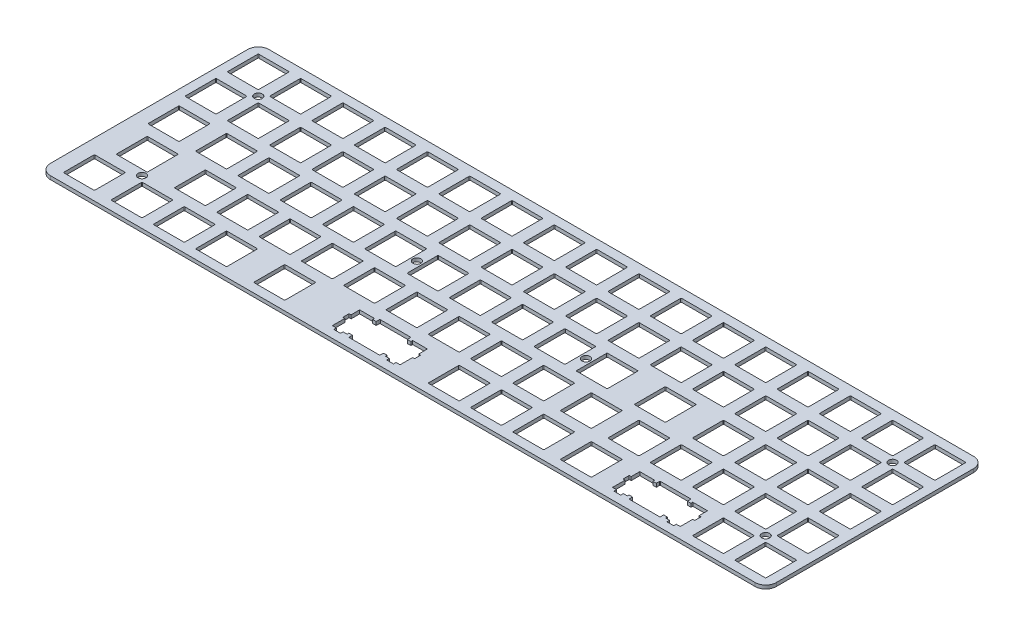
SolidWorks part; units mm, degrees
ref_plane "Front" through (0, 0, 0) normal (0, 0, 1) x (1, 0, 0)
ref_plane "Top" through (0, 0, 0) normal (0, 1, 0) x (1, 0, 0)
ref_plane "Right" through (0, 0, 0) normal (1, 0, 0) x (0, 0, -1)
sketch "Sketch1" plane through (0, 0, 0) normal (0, 1, 0) x (1, 0, 0)
  line L0 (-161.925, 28.575) -> (161.925, 28.575)
  line L1 (161.925, -47.625) -> (-161.925, -47.625)
  line L2 (161.925, -47.625) -> (161.925, 47.625)
  line L3 (161.925, 47.625) -> (-161.925, 47.625)
  line L4 (-161.925, -47.625) -> (-161.925, 47.625)
  line L5 (-123.825, 47.625) -> (-123.825, 28.575)
  line L6 (-104.775, 47.625) -> (-104.775, 28.575)
  line L7 (-142.875, 47.625) -> (-142.875, 28.575)
  line L8 (-85.725, 47.625) -> (-85.725, 28.575)
  line L9 (-66.675, 47.625) -> (-66.675, 28.575)
  line L10 (-47.625, 47.625) -> (-47.625, 28.575)
  line L11 (-28.575, 47.625) -> (-28.575, 28.575)
  line L12 (-9.525, 47.625) -> (-9.525, 28.575)
  line L13 (9.525, 47.625) -> (9.525, 28.575)
  line L14 (28.575, 47.625) -> (28.575, 28.575)
  line L15 (47.625, 47.625) -> (47.625, 28.575)
  line L16 (66.675, 47.625) -> (66.675, 28.575)
  line L17 (85.725, 47.625) -> (85.725, 28.575)
  line L18 (104.775, 47.625) -> (104.775, 28.575)
  line L19 (123.825, 47.625) -> (123.825, 28.575)
  line L20 (142.875, 47.625) -> (142.875, 28.575)
  line L21 (-142.875, 47.625) -> (-123.825, 47.625) construction
  line L22 (-161.925, 9.525) -> (161.925, 9.525)
  line L23 (-142.875, 28.575) -> (-142.875, 9.525)
  line L24 (-123.825, 28.575) -> (-123.825, 9.525)
  line L25 (-104.775, 28.575) -> (-104.775, 9.525)
  line L26 (-85.725, 28.575) -> (-85.725, 9.525)
  line L27 (-66.675, 28.575) -> (-66.675, 9.525)
  line L28 (-47.625, 28.575) -> (-47.625, 9.525)
  line L29 (-28.575, 28.575) -> (-28.575, 9.525)
  line L30 (-9.525, 28.575) -> (-9.525, 9.525)
  line L31 (9.525, 28.575) -> (9.525, 9.525)
  line L32 (28.575, 28.575) -> (28.575, 9.525)
  line L33 (47.625, 28.575) -> (47.625, 9.525)
  line L34 (66.675, 28.575) -> (66.675, 9.525)
  line L35 (85.725, 28.575) -> (85.725, 9.525)
  line L36 (104.775, 28.575) -> (104.775, 9.525)
  line L37 (123.825, 28.575) -> (123.825, 9.525)
  line L38 (142.875, 28.575) -> (142.875, 9.525)
  line L39 (-142.875, 28.575) -> (-123.825, 28.575) construction
  line L40 (-161.925, -9.525) -> (161.925, -9.525)
  line L41 (-161.925, -28.575) -> (161.925, -28.575)
  line L42 (-138.1125, 9.525) -> (-138.1125, -9.525)
  line L43 (-128.5875, -9.525) -> (-128.5875, -28.575)
  line L44 (-138.1125, -28.575) -> (-138.1125, -47.625)
  line L45 (-119.0625, 9.525) -> (-119.0625, -9.525)
  line L46 (-100.0125, 9.525) -> (-100.0125, -9.525)
  line L47 (-80.9625, 9.525) -> (-80.9625, -9.525)
  line L48 (-61.9125, 9.525) -> (-61.9125, -9.525)
  line L49 (-42.8625, 9.525) -> (-42.8625, -9.525)
  line L50 (-23.8125, 9.525) -> (-23.8125, -9.525)
  line L51 (-4.7625, 9.525) -> (-4.7625, -9.525)
  line L52 (14.2875, 9.525) -> (14.2875, -9.525)
  line L53 (33.3375, 9.525) -> (33.3375, -9.525)
  line L54 (-138.1125, 9.525) -> (-119.0625, 9.525) construction
  line L55 (52.3875, 9.525) -> (52.3875, -9.525)
  line L56 (85.725, 9.525) -> (85.725, -9.525)
  line L57 (-109.5375, -9.525) -> (-109.5375, -28.575)
  line L58 (-90.4875, -9.525) -> (-90.4875, -28.575)
  line L59 (-71.4375, -9.525) -> (-71.4375, -28.575)
  line L60 (-52.3875, -9.525) -> (-52.3875, -28.575)
  line L61 (-33.3375, -9.525) -> (-33.3375, -28.575)
  line L62 (-14.2875, -9.525) -> (-14.2875, -28.575)
  line L63 (4.7625, -9.525) -> (4.7625, -28.575)
  line L64 (23.8125, -9.525) -> (23.8125, -28.575)
  line L65 (42.8625, -9.525) -> (42.8625, -28.575)
  line L66 (-128.5875, -9.525) -> (-109.5375, -9.525) construction
  line L67 (66.675, -9.525) -> (66.675, -28.575)
  line L68 (85.725, -9.525) -> (85.725, -28.575)
  line L69 (-119.0625, -28.575) -> (-119.0625, -47.625)
  line L70 (-100.0125, -28.575) -> (-100.0125, -47.625)
  line L71 (-80.9625, -28.575) -> (-80.9625, -47.625)
  line L72 (-138.1125, -28.575) -> (-119.0625, -28.575) construction
  line L73 (-47.625, -28.575) -> (-47.625, -47.625)
  line L74 (4.7625, -28.575) -> (4.7625, -47.625)
  line L75 (23.8125, -28.575) -> (23.8125, -47.625)
  line L76 (42.8625, -28.575) -> (42.8625, -47.625)
  line L77 (61.9125, -28.575) -> (61.9125, -47.625)
  line L78 (85.725, -28.575) -> (85.725, -47.625)
  line L79 (104.775, 9.525) -> (104.775, -9.525)
  line L80 (104.775, -9.525) -> (104.775, -28.575)
  line L81 (123.825, 9.525) -> (123.825, -9.525)
  line L82 (123.825, -9.525) -> (123.825, -28.575)
  line L83 (123.825, -28.575) -> (123.825, -47.625)
  line L84 (142.875, 9.525) -> (142.875, -9.525)
  line L85 (142.875, -9.525) -> (142.875, -28.575)
  line L86 (142.875, -28.575) -> (142.875, -47.625)
  line L87 (-161.925, 47.625) -> (-142.875, 28.575) construction
  line L88 (-142.875, 28.575) -> (-161.925, 9.525) construction
  line L89 (-161.925, 9.525) -> (-138.1125, -9.525) construction
  line L90 (-138.1125, -9.525) -> (-119.0625, 9.525) construction
  line L91 (-119.0625, 9.525) -> (-100.0125, -9.525) construction
  line L92 (-100.0125, -9.525) -> (-80.9625, 9.525) construction
  line L93 (-80.9625, 9.525) -> (-61.9125, -9.525) construction
  line L94 (-61.9125, -9.525) -> (-42.8625, 9.525) construction
  line L95 (-42.8625, 9.525) -> (-23.8125, -9.525) construction
  line L96 (-23.8125, -9.525) -> (-4.7625, 9.525) construction
  line L97 (-4.7625, 9.525) -> (14.2875, -9.525) construction
  line L98 (14.2875, -9.525) -> (33.3375, 9.525) construction
  line L99 (33.3375, 9.525) -> (52.3875, -9.525) construction
  line L100 (52.3875, -9.525) -> (85.725, 9.525) construction
  line L101 (85.725, 9.525) -> (104.775, -9.525) construction
  line L102 (104.775, -9.525) -> (85.725, -28.575) construction
  line L103 (85.725, -47.625) -> (123.825, -28.575) construction
  line L104 (85.725, -28.575) -> (123.825, -47.625) construction
  line L105 (123.825, -28.575) -> (104.775, -9.525) construction
  line L106 (104.775, -9.525) -> (123.825, 9.525) construction
  line L107 (123.825, 9.525) -> (104.775, 28.575) construction
  line L108 (104.775, 28.575) -> (123.825, 47.625) construction
  line L109 (123.825, 47.625) -> (142.875, 28.575) construction
  line L110 (142.875, 28.575) -> (123.825, 9.525) construction
  line L111 (123.825, 9.525) -> (142.875, -9.525) construction
  line L112 (142.875, -9.525) -> (123.825, -28.575) construction
  line L113 (123.825, -28.575) -> (142.875, -47.625) construction
  line L114 (142.875, -47.625) -> (161.925, -28.575) construction
  line L115 (161.925, -28.575) -> (142.875, -9.525) construction
  line L116 (142.875, -9.525) -> (161.925, 9.525) construction
  line L117 (161.925, 9.525) -> (142.875, 28.575) construction
  line L118 (142.875, 28.575) -> (161.925, 47.625) construction
  line L119 (161.925, -47.625) -> (142.875, -28.575) construction
  line L120 (142.875, -28.575) -> (123.825, -47.625) construction
  line L121 (85.725, -47.625) -> (61.9125, -28.575) construction
  line L122 (61.9125, -28.575) -> (42.8625, -47.625) construction
  line L123 (42.8625, -47.625) -> (23.8125, -28.575) construction
  line L124 (23.8125, -28.575) -> (42.8625, -9.525) construction
  line L125 (42.8625, -9.525) -> (66.675, -28.575) construction
  line L126 (66.675, -28.575) -> (85.725, -9.525) construction
  line L127 (85.725, -9.525) -> (104.775, -28.575) construction
  line L128 (104.775, -28.575) -> (123.825, -9.525) construction
  line L129 (123.825, -9.525) -> (142.875, -28.575) construction
  line L130 (142.875, -28.575) -> (161.925, -9.525) construction
  line L131 (161.925, -9.525) -> (142.875, 9.525) construction
  line L132 (142.875, 9.525) -> (123.825, -9.525) construction
  line L133 (123.825, -9.525) -> (104.775, 9.525) construction
  line L134 (104.775, 9.525) -> (85.725, -9.525) construction
  line L135 (85.725, -9.525) -> (52.3875, 9.525) construction
  line L136 (52.3875, 9.525) -> (33.3375, -9.525) construction
  line L137 (33.3375, -9.525) -> (14.2875, 9.525) construction
  line L138 (14.2875, 9.525) -> (-4.7625, -9.525) construction
  line L139 (-4.7625, -9.525) -> (-23.8125, 9.525) construction
  line L140 (-23.8125, 9.525) -> (-42.8625, -9.525) construction
  line L141 (-42.8625, -9.525) -> (-61.9125, 9.525) construction
  line L142 (-61.9125, 9.525) -> (-80.9625, -9.525) construction
  line L143 (-80.9625, -9.525) -> (-100.0125, 9.525) construction
  line L144 (-100.0125, 9.525) -> (-119.0625, -9.525) construction
  line L145 (-119.0625, -9.525) -> (-138.1125, 9.525) construction
  line L146 (-138.1125, 9.525) -> (-161.925, -9.525) construction
  line L147 (-161.925, -9.525) -> (-128.5875, -28.575) construction
  line L148 (-128.5875, -28.575) -> (-109.5375, -9.525) construction
  line L149 (-109.5375, -9.525) -> (-90.4875, -28.575) construction
  line L150 (-90.4875, -28.575) -> (-71.4375, -9.525) construction
  line L151 (-71.4375, -9.525) -> (-52.3875, -28.575) construction
  line L152 (-52.3875, -28.575) -> (-33.3375, -9.525) construction
  line L153 (-33.3375, -9.525) -> (-14.2875, -28.575) construction
  line L154 (-14.2875, -28.575) -> (4.7625, -9.525) construction
  line L155 (4.7625, -9.525) -> (23.8125, -28.575) construction
  line L156 (23.8125, -28.575) -> (4.7625, -47.625) construction
  line L157 (4.7625, -47.625) -> (-47.625, -28.575) construction
  line L158 (-47.625, -28.575) -> (-80.9625, -47.625) construction
  line L159 (-80.9625, -47.625) -> (-100.0125, -28.575) construction
  line L160 (-100.0125, -28.575) -> (-119.0625, -47.625) construction
  line L161 (-119.0625, -47.625) -> (-138.1125, -28.575) construction
  line L162 (-138.1125, -28.575) -> (-161.925, -47.625) construction
  line L163 (-161.925, -28.575) -> (-138.1125, -47.625) construction
  line L164 (-138.1125, -47.625) -> (-119.0625, -28.575) construction
  line L165 (-119.0625, -28.575) -> (-100.0125, -47.625) construction
  line L166 (-100.0125, -47.625) -> (-80.9625, -28.575) construction
  line L167 (-80.9625, -28.575) -> (-47.625, -47.625) construction
  line L168 (-47.625, -47.625) -> (4.7625, -28.575) construction
  line L169 (4.7625, -28.575) -> (23.8125, -47.625) construction
  line L170 (23.8125, -47.625) -> (42.8625, -28.575) construction
  line L171 (42.8625, -28.575) -> (61.9125, -47.625) construction
  line L172 (61.9125, -47.625) -> (85.725, -28.575) construction
  line L173 (85.725, -28.575) -> (66.675, -9.525) construction
  line L174 (66.675, -9.525) -> (42.8625, -28.575) construction
  line L175 (42.8625, -28.575) -> (23.8125, -9.525) construction
  line L176 (23.8125, -9.525) -> (4.7625, -28.575) construction
  line L177 (4.7625, -28.575) -> (-14.2875, -9.525) construction
  line L178 (-14.2875, -9.525) -> (-33.3375, -28.575) construction
  line L179 (-33.3375, -28.575) -> (-52.3875, -9.525) construction
  line L180 (-52.3875, -9.525) -> (-71.4375, -28.575) construction
  line L181 (-71.4375, -28.575) -> (-90.4875, -9.525) construction
  line L182 (-90.4875, -9.525) -> (-109.5375, -28.575) construction
  line L183 (-109.5375, -28.575) -> (-128.5875, -9.525) construction
  line L184 (-128.5875, -9.525) -> (-161.925, -28.575) construction
  line L185 (161.925, 28.575) -> (142.875, 9.525) construction
  line L186 (142.875, 9.525) -> (123.825, 28.575) construction
  line L187 (123.825, 28.575) -> (104.775, 9.525) construction
  line L188 (104.775, 9.525) -> (85.725, 28.575) construction
  line L189 (85.725, 28.575) -> (66.675, 9.525) construction
  line L190 (66.675, 9.525) -> (47.625, 28.575) construction
  line L191 (47.625, 28.575) -> (28.575, 9.525) construction
  line L192 (28.575, 9.525) -> (9.525, 28.575) construction
  line L193 (9.525, 28.575) -> (-9.525, 9.525) construction
  line L194 (-9.525, 9.525) -> (-28.575, 28.575) construction
  line L195 (-28.575, 28.575) -> (-47.625, 9.525) construction
  line L196 (-47.625, 9.525) -> (-66.675, 28.575) construction
  line L197 (-66.675, 28.575) -> (-85.725, 9.525) construction
  line L198 (-85.725, 9.525) -> (-104.775, 28.575) construction
  line L199 (-104.775, 28.575) -> (-123.825, 9.525) construction
  line L200 (-123.825, 9.525) -> (-142.875, 28.575) construction
  line L201 (-161.925, 28.575) -> (-142.875, 9.525) construction
  line L202 (-142.875, 9.525) -> (-123.825, 28.575) construction
  line L203 (-123.825, 28.575) -> (-104.775, 9.525) construction
  line L204 (-104.775, 9.525) -> (-85.725, 28.575) construction
  line L205 (-85.725, 28.575) -> (-66.675, 9.525) construction
  line L206 (-66.675, 9.525) -> (-47.625, 28.575) construction
  line L207 (-47.625, 28.575) -> (-28.575, 9.525) construction
  line L208 (-28.575, 9.525) -> (-9.525, 28.575) construction
  line L209 (-9.525, 28.575) -> (9.525, 9.525) construction
  line L210 (9.525, 9.525) -> (28.575, 28.575) construction
  line L211 (28.575, 28.575) -> (47.625, 9.525) construction
  line L212 (47.625, 9.525) -> (66.675, 28.575) construction
  line L213 (66.675, 28.575) -> (85.725, 9.525) construction
  line L214 (85.725, 9.525) -> (104.775, 28.575) construction
  line L215 (161.925, 28.575) -> (142.875, 47.625) construction
  line L216 (142.875, 47.625) -> (123.825, 28.575) construction
  line L217 (123.825, 28.575) -> (104.775, 47.625) construction
  line L218 (104.775, 47.625) -> (85.725, 28.575) construction
  line L219 (85.725, 28.575) -> (66.675, 47.625) construction
  line L220 (66.675, 47.625) -> (47.625, 28.575) construction
  line L221 (47.625, 28.575) -> (28.575, 47.625) construction
  line L222 (28.575, 47.625) -> (9.525, 28.575) construction
  line L223 (9.525, 28.575) -> (-9.525, 47.625) construction
  line L224 (-9.525, 47.625) -> (-28.575, 28.575) construction
  line L225 (-28.575, 28.575) -> (-47.625, 47.625) construction
  line L226 (-47.625, 47.625) -> (-66.675, 28.575) construction
  line L227 (-66.675, 28.575) -> (-85.725, 47.625) construction
  line L228 (-85.725, 47.625) -> (-104.775, 28.575) construction
  line L229 (-104.775, 28.575) -> (-123.825, 47.625) construction
  line L230 (-123.825, 47.625) -> (-142.875, 28.575) construction
  line L231 (-161.925, 28.575) -> (-142.875, 47.625) construction
  line L232 (-142.875, 47.625) -> (-123.825, 28.575) construction
  line L233 (-123.825, 28.575) -> (-104.775, 47.625) construction
  line L234 (-104.775, 47.625) -> (-85.725, 28.575) construction
  line L235 (-85.725, 28.575) -> (-66.675, 47.625) construction
  line L236 (-66.675, 47.625) -> (-47.625, 28.575) construction
  line L237 (-47.625, 28.575) -> (-28.575, 47.625) construction
  line L238 (-28.575, 47.625) -> (-9.525, 28.575) construction
  line L239 (-9.525, 28.575) -> (9.525, 47.625) construction
  line L240 (9.525, 47.625) -> (28.575, 28.575) construction
  line L241 (28.575, 28.575) -> (47.625, 47.625) construction
  line L242 (47.625, 47.625) -> (66.675, 28.575) construction
  line L243 (66.675, 28.575) -> (85.725, 47.625) construction
  line L244 (85.725, 47.625) -> (104.775, 28.575) construction
  line L245 (160.147, 50.6095) -> (-160.147, 50.6095)
  line L246 (164.9095, 45.847) -> (164.9095, -45.847)
  line L247 (160.147, -50.6095) -> (-160.147, -50.6095)
  line L248 (-164.9095, 45.847) -> (-164.9095, -45.847)
  arc A0 (164.9095, 45.847) -> (160.147, 50.6095) centre (160.147, 45.847) ccw
  arc A1 (160.147, -50.6095) -> (164.9095, -45.847) centre (160.147, -45.847) ccw
  arc A2 (-164.9095, -45.847) -> (-160.147, -50.6095) centre (-160.147, -45.847) ccw
  arc A3 (-160.147, 50.6095) -> (-164.9095, 45.847) centre (-160.147, 45.847) ccw
  point P145 (0, 0)
  point P146 (104.775, -38.1)
  point P147 (-152.4, 38.1)
  point P148 (-152.4, 19.05)
  point P149 (-150.0188, 0)
  point P150 (-145.2562, -19.05)
  point P151 (-150.0188, -38.1)
  point P152 (-128.5875, -38.1)
  point P153 (-119.0625, -19.05)
  point P154 (-128.5875, 0)
  point P155 (-133.35, 19.05)
  point P156 (-133.35, 38.1)
  point P157 (-114.3, 38.1)
  point P158 (-114.3, 19.05)
  point P159 (-109.5375, 0)
  point P160 (-100.0125, -19.05)
  point P161 (-90.4875, -38.1)
  point P162 (-109.5375, -38.1)
  point P163 (-64.2938, -38.1)
  point P164 (-21.4312, -38.1)
  point P165 (14.2875, -38.1)
  point P166 (33.3375, -38.1)
  point P167 (52.3875, -38.1)
  point P168 (73.8188, -38.1)
  point P169 (133.35, -38.1)
  point P170 (152.4, -38.1)
  point P171 (152.4, -19.05)
  point P172 (133.35, -19.05)
  point P173 (114.3, -19.05)
  point P174 (95.25, -19.05)
  point P175 (76.2, -19.05)
  point P176 (54.7687, -19.05)
  point P177 (33.3375, -19.05)
  point P178 (14.2875, -19.05)
  point P179 (-4.7625, -19.05)
  point P180 (-23.8125, -19.05)
  point P181 (-42.8625, -19.05)
  point P182 (-61.9125, -19.05)
  point P183 (-80.9625, -19.05)
  point P184 (-90.4875, 0)
  point P185 (-71.4375, 0)
  point P186 (-52.3875, 0)
  point P187 (-33.3375, 0)
  point P188 (-14.2875, 0)
  point P189 (4.7625, 0)
  point P190 (23.8125, 0)
  point P191 (42.8625, 0)
  point P192 (69.0563, 0)
  point P193 (95.25, 0)
  point P194 (114.3, 0)
  point P195 (133.35, 0)
  point P196 (152.4, 0)
  point P197 (152.4, 19.05)
  point P198 (133.35, 19.05)
  point P199 (114.3, 19.05)
  point P200 (95.25, 19.05)
  point P201 (76.2, 19.05)
  point P202 (57.15, 19.05)
  point P203 (38.1, 19.05)
  point P204 (19.05, 19.05)
  point P205 (0, 19.05)
  point P206 (-19.05, 19.05)
  point P207 (-38.1, 19.05)
  point P208 (-57.15, 19.05)
  point P209 (-76.2, 19.05)
  point P210 (-95.25, 19.05)
  point P211 (-95.25, 38.1)
  point P212 (-76.2, 38.1)
  point P213 (-57.15, 38.1)
  point P214 (-38.1, 38.1)
  point P215 (-19.05, 38.1)
  point P216 (0, 38.1)
  point P217 (19.05, 38.1)
  point P218 (38.1, 38.1)
  point P219 (57.15, 38.1)
  point P220 (76.2, 38.1)
  point P221 (95.25, 38.1)
  point P222 (114.3, 38.1)
  point P223 (133.35, 38.1)
  point P224 (152.4, 38.1)
  point P225 (-152.4, 38.1)
  point P226 (0, 0)
sketch "Sketch2" plane through (0, 0, 0) normal (0, 1, 0) x (1, 0, 0)
  line L0 (-161.925, 28.575) -> (-142.875, 47.625) construction
  line L1 (-145.7071, 45.0977) -> (-159.0929, 45.0977)
  line L2 (-145.4023, 44.7929) -> (-145.4023, 31.4071)
  line L3 (-145.7071, 31.1023) -> (-159.0929, 31.1023)
  line L4 (-159.3977, 44.7929) -> (-159.3977, 31.4071)
  line L5 (-152.4, 31.1023) -> (-152.4, 45.0977) construction
  line L6 (-145.4023, 38.1) -> (-159.3977, 38.1) construction
  line L7 (-126.3523, 38.1) -> (-140.3477, 38.1) construction
  line L8 (-133.35, 31.1023) -> (-133.35, 45.0977) construction
  line L9 (-126.6571, 45.0977) -> (-140.0429, 45.0977)
  line L10 (-126.3523, 44.7929) -> (-126.3523, 31.4071)
  line L11 (-140.3477, 44.7929) -> (-140.3477, 31.4071)
  line L12 (-126.6571, 31.1023) -> (-140.0429, 31.1023)
  line L13 (-107.3023, 38.1) -> (-121.2977, 38.1) construction
  line L14 (-114.3, 31.1023) -> (-114.3, 45.0977) construction
  line L15 (-107.6071, 45.0977) -> (-120.9929, 45.0977)
  line L16 (-107.3023, 44.7929) -> (-107.3023, 31.4071)
  line L17 (-121.2977, 44.7929) -> (-121.2977, 31.4071)
  line L18 (-107.6071, 31.1023) -> (-120.9929, 31.1023)
  line L19 (-88.2523, 38.1) -> (-102.2477, 38.1) construction
  line L20 (-95.25, 31.1023) -> (-95.25, 45.0977) construction
  line L21 (-88.5571, 45.0977) -> (-101.9429, 45.0977)
  line L22 (-88.2523, 44.7929) -> (-88.2523, 31.4071)
  line L23 (-102.2477, 44.7929) -> (-102.2477, 31.4071)
  line L24 (-88.5571, 31.1023) -> (-101.9429, 31.1023)
  line L25 (-69.2023, 38.1) -> (-83.1977, 38.1) construction
  line L26 (-76.2, 31.1023) -> (-76.2, 45.0977) construction
  line L27 (-69.5071, 45.0977) -> (-82.8929, 45.0977)
  line L28 (-69.2023, 44.7929) -> (-69.2023, 31.4071)
  line L29 (-83.1977, 44.7929) -> (-83.1977, 31.4071)
  line L30 (-69.5071, 31.1023) -> (-82.8929, 31.1023)
  line L31 (-50.1523, 38.1) -> (-64.1477, 38.1) construction
  line L32 (-57.15, 31.1023) -> (-57.15, 45.0977) construction
  line L33 (-50.4571, 45.0977) -> (-63.8429, 45.0977)
  line L34 (-50.1523, 44.7929) -> (-50.1523, 31.4071)
  line L35 (-64.1477, 44.7929) -> (-64.1477, 31.4071)
  line L36 (-50.4571, 31.1023) -> (-63.8429, 31.1023)
  line L37 (-31.1023, 38.1) -> (-45.0977, 38.1) construction
  line L38 (-38.1, 31.1023) -> (-38.1, 45.0977) construction
  line L39 (-31.4071, 45.0977) -> (-44.7929, 45.0977)
  line L40 (-31.1023, 44.7929) -> (-31.1023, 31.4071)
  line L41 (-45.0977, 44.7929) -> (-45.0977, 31.4071)
  line L42 (-31.4071, 31.1023) -> (-44.7929, 31.1023)
  line L43 (-12.0523, 38.1) -> (-26.0477, 38.1) construction
  line L44 (-19.05, 31.1023) -> (-19.05, 45.0977) construction
  line L45 (-12.3571, 45.0977) -> (-25.7429, 45.0977)
  line L46 (-12.0523, 44.7929) -> (-12.0523, 31.4071)
  line L47 (-26.0477, 44.7929) -> (-26.0477, 31.4071)
  line L48 (-12.3571, 31.1023) -> (-25.7429, 31.1023)
  line L49 (6.9977, 38.1) -> (-6.9977, 38.1) construction
  line L50 (0, 31.1023) -> (0, 45.0977) construction
  line L51 (6.6929, 45.0977) -> (-6.6929, 45.0977)
  line L52 (6.9977, 44.7929) -> (6.9977, 31.4071)
  line L53 (-6.9977, 44.7929) -> (-6.9977, 31.4071)
  line L54 (6.6929, 31.1023) -> (-6.6929, 31.1023)
  line L55 (26.0477, 38.1) -> (12.0523, 38.1) construction
  line L56 (19.05, 31.1023) -> (19.05, 45.0977) construction
  line L57 (25.7429, 45.0977) -> (12.3571, 45.0977)
  line L58 (26.0477, 44.7929) -> (26.0477, 31.4071)
  line L59 (12.0523, 44.7929) -> (12.0523, 31.4071)
  line L60 (25.7429, 31.1023) -> (12.3571, 31.1023)
  line L61 (45.0977, 38.1) -> (31.1023, 38.1) construction
  line L62 (38.1, 31.1023) -> (38.1, 45.0977) construction
  line L63 (44.7929, 45.0977) -> (31.4071, 45.0977)
  line L64 (45.0977, 44.7929) -> (45.0977, 31.4071)
  line L65 (31.1023, 44.7929) -> (31.1023, 31.4071)
  line L66 (44.7929, 31.1023) -> (31.4071, 31.1023)
  line L67 (64.1477, 38.1) -> (50.1523, 38.1) construction
  line L68 (57.15, 31.1023) -> (57.15, 45.0977) construction
  line L69 (63.8429, 45.0977) -> (50.4571, 45.0977)
  line L70 (64.1477, 44.7929) -> (64.1477, 31.4071)
  line L71 (50.1523, 44.7929) -> (50.1523, 31.4071)
  line L72 (63.8429, 31.1023) -> (50.4571, 31.1023)
  line L73 (83.1977, 38.1) -> (69.2023, 38.1) construction
  line L74 (76.2, 31.1023) -> (76.2, 45.0977) construction
  line L75 (82.8929, 45.0977) -> (69.5071, 45.0977)
  line L76 (83.1977, 44.7929) -> (83.1977, 31.4071)
  line L77 (69.2023, 44.7929) -> (69.2023, 31.4071)
  line L78 (82.8929, 31.1023) -> (69.5071, 31.1023)
  line L79 (102.2477, 38.1) -> (88.2523, 38.1) construction
  line L80 (95.25, 31.1023) -> (95.25, 45.0977) construction
  line L81 (101.9429, 45.0977) -> (88.5571, 45.0977)
  line L82 (102.2477, 44.7929) -> (102.2477, 31.4071)
  line L83 (88.2523, 44.7929) -> (88.2523, 31.4071)
  line L84 (101.9429, 31.1023) -> (88.5571, 31.1023)
  line L85 (121.2977, 38.1) -> (107.3023, 38.1) construction
  line L86 (114.3, 31.1023) -> (114.3, 45.0977) construction
  line L87 (120.9929, 45.0977) -> (107.6071, 45.0977)
  line L88 (121.2977, 44.7929) -> (121.2977, 31.4071)
  line L89 (107.3023, 44.7929) -> (107.3023, 31.4071)
  line L90 (120.9929, 31.1023) -> (107.6071, 31.1023)
  line L91 (140.3477, 38.1) -> (126.3523, 38.1) construction
  line L92 (133.35, 31.1023) -> (133.35, 45.0977) construction
  line L93 (140.0429, 45.0977) -> (126.6571, 45.0977)
  line L94 (140.3477, 44.7929) -> (140.3477, 31.4071)
  line L95 (126.3523, 44.7929) -> (126.3523, 31.4071)
  line L96 (140.0429, 31.1023) -> (126.6571, 31.1023)
  line L97 (159.3977, 38.1) -> (145.4023, 38.1) construction
  line L98 (152.4, 31.1023) -> (152.4, 45.0977) construction
  line L99 (159.0929, 45.0977) -> (145.7071, 45.0977)
  line L100 (159.3977, 44.7929) -> (159.3977, 31.4071)
  line L101 (145.4023, 44.7929) -> (145.4023, 31.4071)
  line L102 (159.0929, 31.1023) -> (145.7071, 31.1023)
  line L103 (-126.3523, 19.05) -> (-140.3477, 19.05) construction
  line L104 (-133.35, 12.0523) -> (-133.35, 26.0477) construction
  line L105 (-126.6571, 26.0477) -> (-140.0429, 26.0477)
  line L106 (-126.3523, 25.7429) -> (-126.3523, 12.3571)
  line L107 (-140.3477, 25.7429) -> (-140.3477, 12.3571)
  line L108 (-126.6571, 12.0523) -> (-140.0429, 12.0523)
  line L109 (-107.3023, 19.05) -> (-121.2977, 19.05) construction
  line L110 (-114.3, 12.0523) -> (-114.3, 26.0477) construction
  line L111 (-107.6071, 26.0477) -> (-120.9929, 26.0477)
  line L112 (-107.3023, 25.7429) -> (-107.3023, 12.3571)
  line L113 (-121.2977, 25.7429) -> (-121.2977, 12.3571)
  line L114 (-107.6071, 12.0523) -> (-120.9929, 12.0523)
  line L115 (-88.2523, 19.05) -> (-102.2477, 19.05) construction
  line L116 (-95.25, 12.0523) -> (-95.25, 26.0477) construction
  line L117 (-88.5571, 26.0477) -> (-101.9429, 26.0477)
  line L118 (-88.2523, 25.7429) -> (-88.2523, 12.3571)
  line L119 (-102.2477, 25.7429) -> (-102.2477, 12.3571)
  line L120 (-88.5571, 12.0523) -> (-101.9429, 12.0523)
  line L121 (-69.2023, 19.05) -> (-83.1977, 19.05) construction
  line L122 (-76.2, 12.0523) -> (-76.2, 26.0477) construction
  line L123 (-69.5071, 26.0477) -> (-82.8929, 26.0477)
  line L124 (-69.2023, 25.7429) -> (-69.2023, 12.3571)
  line L125 (-83.1977, 25.7429) -> (-83.1977, 12.3571)
  line L126 (-69.5071, 12.0523) -> (-82.8929, 12.0523)
  line L127 (-50.1523, 19.05) -> (-64.1477, 19.05) construction
  line L128 (-57.15, 12.0523) -> (-57.15, 26.0477) construction
  line L129 (-50.4571, 26.0477) -> (-63.8429, 26.0477)
  line L130 (-50.1523, 25.7429) -> (-50.1523, 12.3571)
  line L131 (-64.1477, 25.7429) -> (-64.1477, 12.3571)
  line L132 (-50.4571, 12.0523) -> (-63.8429, 12.0523)
  line L133 (-31.1023, 19.05) -> (-45.0977, 19.05) construction
  line L134 (-38.1, 12.0523) -> (-38.1, 26.0477) construction
  line L135 (-31.4071, 26.0477) -> (-44.7929, 26.0477)
  line L136 (-31.1023, 25.7429) -> (-31.1023, 12.3571)
  line L137 (-45.0977, 25.7429) -> (-45.0977, 12.3571)
  line L138 (-31.4071, 12.0523) -> (-44.7929, 12.0523)
  line L139 (-12.0523, 19.05) -> (-26.0477, 19.05) construction
  line L140 (-19.05, 12.0523) -> (-19.05, 26.0477) construction
  line L141 (-12.3571, 26.0477) -> (-25.7429, 26.0477)
  line L142 (-12.0523, 25.7429) -> (-12.0523, 12.3571)
  line L143 (-26.0477, 25.7429) -> (-26.0477, 12.3571)
  line L144 (-12.3571, 12.0523) -> (-25.7429, 12.0523)
  line L145 (6.9977, 19.05) -> (-6.9977, 19.05) construction
  line L146 (0, 12.0523) -> (0, 26.0477) construction
  line L147 (6.6929, 26.0477) -> (-6.6929, 26.0477)
  line L148 (6.9977, 25.7429) -> (6.9977, 12.3571)
  line L149 (-6.9977, 25.7429) -> (-6.9977, 12.3571)
  line L150 (6.6929, 12.0523) -> (-6.6929, 12.0523)
  line L151 (26.0477, 19.05) -> (12.0523, 19.05) construction
  line L152 (19.05, 12.0523) -> (19.05, 26.0477) construction
  line L153 (25.7429, 26.0477) -> (12.3571, 26.0477)
  line L154 (26.0477, 25.7429) -> (26.0477, 12.3571)
  line L155 (12.0523, 25.7429) -> (12.0523, 12.3571)
  line L156 (25.7429, 12.0523) -> (12.3571, 12.0523)
  line L157 (45.0977, 19.05) -> (31.1023, 19.05) construction
  line L158 (38.1, 12.0523) -> (38.1, 26.0477) construction
  line L159 (44.7929, 26.0477) -> (31.4071, 26.0477)
  line L160 (45.0977, 25.7429) -> (45.0977, 12.3571)
  line L161 (31.1023, 25.7429) -> (31.1023, 12.3571)
  line L162 (44.7929, 12.0523) -> (31.4071, 12.0523)
  line L163 (64.1477, 19.05) -> (50.1523, 19.05) construction
  line L164 (57.15, 12.0523) -> (57.15, 26.0477) construction
  line L165 (63.8429, 26.0477) -> (50.4571, 26.0477)
  line L166 (64.1477, 25.7429) -> (64.1477, 12.3571)
  line L167 (50.1523, 25.7429) -> (50.1523, 12.3571)
  line L168 (63.8429, 12.0523) -> (50.4571, 12.0523)
  line L169 (83.1977, 19.05) -> (69.2023, 19.05) construction
  line L170 (76.2, 12.0523) -> (76.2, 26.0477) construction
  line L171 (82.8929, 26.0477) -> (69.5071, 26.0477)
  line L172 (83.1977, 25.7429) -> (83.1977, 12.3571)
  line L173 (69.2023, 25.7429) -> (69.2023, 12.3571)
  line L174 (82.8929, 12.0523) -> (69.5071, 12.0523)
  line L175 (102.2477, 19.05) -> (88.2523, 19.05) construction
  line L176 (95.25, 12.0523) -> (95.25, 26.0477) construction
  line L177 (101.9429, 26.0477) -> (88.5571, 26.0477)
  line L178 (102.2477, 25.7429) -> (102.2477, 12.3571)
  line L179 (88.2523, 25.7429) -> (88.2523, 12.3571)
  line L180 (101.9429, 12.0523) -> (88.5571, 12.0523)
  line L181 (121.2977, 19.05) -> (107.3023, 19.05) construction
  line L182 (114.3, 12.0523) -> (114.3, 26.0477) construction
  line L183 (120.9929, 26.0477) -> (107.6071, 26.0477)
  line L184 (121.2977, 25.7429) -> (121.2977, 12.3571)
  line L185 (107.3023, 25.7429) -> (107.3023, 12.3571)
  line L186 (120.9929, 12.0523) -> (107.6071, 12.0523)
  line L187 (140.3477, 19.05) -> (126.3523, 19.05) construction
  line L188 (133.35, 12.0523) -> (133.35, 26.0477) construction
  line L189 (140.0429, 26.0477) -> (126.6571, 26.0477)
  line L190 (140.3477, 25.7429) -> (140.3477, 12.3571)
  line L191 (126.3523, 25.7429) -> (126.3523, 12.3571)
  line L192 (140.0429, 12.0523) -> (126.6571, 12.0523)
  line L193 (159.3977, 19.05) -> (145.4023, 19.05) construction
  line L194 (152.4, 12.0523) -> (152.4, 26.0477) construction
  line L195 (159.0929, 26.0477) -> (145.7071, 26.0477)
  line L196 (159.3977, 25.7429) -> (159.3977, 12.3571)
  line L197 (145.4023, 25.7429) -> (145.4023, 12.3571)
  line L198 (159.0929, 12.0523) -> (145.7071, 12.0523)
  line L199 (-145.4023, 19.05) -> (-159.3977, 19.05) construction
  line L200 (-152.4, 12.0523) -> (-152.4, 26.0477) construction
  line L201 (-145.7071, 26.0477) -> (-159.0929, 26.0477)
  line L202 (-145.4023, 25.7429) -> (-145.4023, 12.3571)
  line L203 (-159.3977, 25.7429) -> (-159.3977, 12.3571)
  line L204 (-145.7071, 12.0523) -> (-159.0929, 12.0523)
  line L205 (-100.0125, -26.0477) -> (-100.0125, -12.0523) construction
  line L210 (-138.1125, 9.525) -> (-161.925, -9.525) construction
  line L211 (-157.0164, -6.9977) -> (-143.021, -6.9977)
  line L212 (-157.0164, -6.9977) -> (-157.0164, 6.9977)
  line L213 (-138.2585, -12.0523) -> (-152.254, -12.0523)
  line L214 (-138.2585, -12.0523) -> (-138.2585, -26.0477)
  line L215 (-138.2585, -26.0477) -> (-152.254, -26.0477)
  line L216 (-152.254, -12.0523) -> (-152.254, -26.0477)
  line L217 (-145.2562, -26.0477) -> (-145.2562, -12.0523) construction
  line L218 (-138.2586, -19.05) -> (-152.254, -19.05) construction
  line L219 (-157.0164, 6.9977) -> (-143.021, 6.9977)
  line L220 (-143.021, -6.9977) -> (-143.021, 6.9977)
  line L221 (-150.0187, 6.9977) -> (-150.0187, -6.9977) construction
  line L222 (-157.0164, 0) -> (-143.021, 0) construction
  line L223 (-138.1125, -28.575) -> (-161.925, -47.625) construction
  line L224 (-143.021, -31.1023) -> (-157.0164, -31.1023)
  line L225 (-143.021, -31.1023) -> (-143.021, -45.0977)
  line L226 (-143.021, -45.0977) -> (-157.0164, -45.0977)
  line L227 (-157.0164, -31.1023) -> (-157.0164, -45.0977)
  line L228 (-150.0187, -45.0977) -> (-150.0187, -31.1023) construction
  line L229 (-143.021, -38.1) -> (-157.0164, -38.1) construction
  line L230 (-128.5875, -28.575) -> (-109.5375, -9.525) construction
  line L231 (-121.5898, 6.9977) -> (-135.5852, 6.9977)
  line L232 (-121.5898, 6.9977) -> (-121.5898, -6.9977)
  line L233 (-121.5898, -6.9977) -> (-135.5852, -6.9977)
  line L234 (-135.5852, 6.9977) -> (-135.5852, -6.9977)
  line L235 (-128.5875, -6.9977) -> (-128.5875, 6.9977) construction
  line L236 (-121.5898, 0) -> (-135.5852, 0) construction
  line L237 (-112.0648, -12.0523) -> (-126.0602, -12.0523)
  line L238 (-112.0648, -12.0523) -> (-112.0648, -26.0477)
  line L239 (-112.0648, -26.0477) -> (-126.0602, -26.0477)
  line L240 (-126.0602, -12.0523) -> (-126.0602, -26.0477)
  line L241 (-119.0625, -26.0477) -> (-119.0625, -12.0523) construction
  line L242 (-112.0648, -19.05) -> (-126.0602, -19.05) construction
  line L243 (-138.1125, -47.625) -> (-119.0625, -28.575) construction
  line L244 (-135.5852, -45.0977) -> (-121.5898, -45.0977)
  line L245 (-135.5852, -45.0977) -> (-135.5852, -31.1023)
  line L246 (-135.5852, -31.1023) -> (-121.5898, -31.1023)
  line L247 (-121.5898, -45.0977) -> (-121.5898, -31.1023)
  line L248 (-128.5875, -31.1023) -> (-128.5875, -45.0977) construction
  line L249 (-135.5852, -38.1) -> (-121.5898, -38.1) construction
  line L250 (-102.5398, -6.9977) -> (-116.5352, -6.9977)
  line L251 (-102.5398, 6.9977) -> (-102.5398, -6.9977)
  line L252 (-102.5398, 6.9977) -> (-116.5352, 6.9977)
  line L253 (-116.5352, 6.9977) -> (-116.5352, -6.9977)
  line L254 (-102.5398, 0) -> (-116.5352, 0) construction
  line L255 (-109.5375, -6.9977) -> (-109.5375, 6.9977) construction
  line L256 (-83.4898, -6.9977) -> (-97.4852, -6.9977)
  line L257 (-83.4898, 6.9977) -> (-83.4898, -6.9977)
  line L258 (-83.4898, 6.9977) -> (-97.4852, 6.9977)
  line L259 (-97.4852, 6.9977) -> (-97.4852, -6.9977)
  line L260 (-83.4898, 0) -> (-97.4852, 0) construction
  line L261 (-90.4875, -6.9977) -> (-90.4875, 6.9977) construction
  line L262 (-64.4398, -6.9977) -> (-78.4352, -6.9977)
  line L263 (-64.4398, 6.9977) -> (-64.4398, -6.9977)
  line L264 (-64.4398, 6.9977) -> (-78.4352, 6.9977)
  line L265 (-78.4352, 6.9977) -> (-78.4352, -6.9977)
  line L266 (-64.4398, 0) -> (-78.4352, 0) construction
  line L267 (-71.4375, -6.9977) -> (-71.4375, 6.9977) construction
  line L268 (-45.3898, -6.9977) -> (-59.3852, -6.9977)
  line L269 (-45.3898, 6.9977) -> (-45.3898, -6.9977)
  line L270 (-45.3898, 6.9977) -> (-59.3852, 6.9977)
  line L271 (-59.3852, 6.9977) -> (-59.3852, -6.9977)
  line L272 (-45.3898, 0) -> (-59.3852, 0) construction
  line L273 (-52.3875, -6.9977) -> (-52.3875, 6.9977) construction
  line L274 (-26.3398, -6.9977) -> (-40.3352, -6.9977)
  line L275 (-26.3398, 6.9977) -> (-26.3398, -6.9977)
  line L276 (-26.3398, 6.9977) -> (-40.3352, 6.9977)
  line L277 (-40.3352, 6.9977) -> (-40.3352, -6.9977)
  line L278 (-26.3398, 0) -> (-40.3352, 0) construction
  line L279 (-33.3375, -6.9977) -> (-33.3375, 6.9977) construction
  line L280 (-7.2898, -6.9977) -> (-21.2852, -6.9977)
  line L281 (-7.2898, 6.9977) -> (-7.2898, -6.9977)
  line L282 (-7.2898, 6.9977) -> (-21.2852, 6.9977)
  line L283 (-21.2852, 6.9977) -> (-21.2852, -6.9977)
  line L284 (-7.2898, 0) -> (-21.2852, 0) construction
  line L285 (-14.2875, -6.9977) -> (-14.2875, 6.9977) construction
  line L286 (11.7602, -6.9977) -> (-2.2352, -6.9977)
  line L287 (11.7602, 6.9977) -> (11.7602, -6.9977)
  line L288 (11.7602, 6.9977) -> (-2.2352, 6.9977)
  line L289 (-2.2352, 6.9977) -> (-2.2352, -6.9977)
  line L290 (11.7602, 0) -> (-2.2352, 0) construction
  line L291 (4.7625, -6.9977) -> (4.7625, 6.9977) construction
  line L292 (30.8102, -6.9977) -> (16.8148, -6.9977)
  line L293 (30.8102, 6.9977) -> (30.8102, -6.9977)
  line L294 (30.8102, 6.9977) -> (16.8148, 6.9977)
  line L295 (16.8148, 6.9977) -> (16.8148, -6.9977)
  line L296 (30.8102, 0) -> (16.8148, 0) construction
  line L297 (23.8125, -6.9977) -> (23.8125, 6.9977) construction
  line L298 (49.8602, -6.9977) -> (35.8648, -6.9977)
  line L299 (49.8602, 6.9977) -> (49.8602, -6.9977)
  line L300 (49.8602, 6.9977) -> (35.8648, 6.9977)
  line L301 (35.8648, 6.9977) -> (35.8648, -6.9977)
  line L302 (49.8602, 0) -> (35.8648, 0) construction
  line L303 (42.8625, -6.9977) -> (42.8625, 6.9977) construction
  line L304 (-93.0148, -19.05) -> (-107.0102, -19.05) construction
  line L305 (-93.0148, -12.0523) -> (-107.0102, -12.0523)
  line L306 (-93.0148, -12.0523) -> (-93.0148, -26.0477)
  line L307 (-93.0148, -26.0477) -> (-107.0102, -26.0477)
  line L308 (-107.0102, -12.0523) -> (-107.0102, -26.0477)
  line L309 (-80.9625, -26.0477) -> (-80.9625, -12.0523) construction
  line L310 (-73.9648, -19.05) -> (-87.9602, -19.05) construction
  line L311 (-73.9648, -12.0523) -> (-87.9602, -12.0523)
  line L312 (-73.9648, -12.0523) -> (-73.9648, -26.0477)
  line L313 (-73.9648, -26.0477) -> (-87.9602, -26.0477)
  line L314 (-87.9602, -12.0523) -> (-87.9602, -26.0477)
  line L315 (-61.9125, -26.0477) -> (-61.9125, -12.0523) construction
  line L316 (-54.9148, -19.05) -> (-68.9102, -19.05) construction
  line L317 (-54.9148, -12.0523) -> (-68.9102, -12.0523)
  line L318 (-54.9148, -12.0523) -> (-54.9148, -26.0477)
  line L319 (-54.9148, -26.0477) -> (-68.9102, -26.0477)
  line L320 (-68.9102, -12.0523) -> (-68.9102, -26.0477)
  line L321 (-42.8625, -26.0477) -> (-42.8625, -12.0523) construction
  line L322 (-35.8648, -19.05) -> (-49.8602, -19.05) construction
  line L323 (-35.8648, -12.0523) -> (-49.8602, -12.0523)
  line L324 (-35.8648, -12.0523) -> (-35.8648, -26.0477)
  line L325 (-35.8648, -26.0477) -> (-49.8602, -26.0477)
  line L326 (-49.8602, -12.0523) -> (-49.8602, -26.0477)
  line L327 (-23.8125, -26.0477) -> (-23.8125, -12.0523) construction
  line L328 (-16.8148, -19.05) -> (-30.8102, -19.05) construction
  line L329 (-16.8148, -12.0523) -> (-30.8102, -12.0523)
  line L330 (-16.8148, -12.0523) -> (-16.8148, -26.0477)
  line L331 (-16.8148, -26.0477) -> (-30.8102, -26.0477)
  line L332 (-30.8102, -12.0523) -> (-30.8102, -26.0477)
  line L333 (-4.7625, -26.0477) -> (-4.7625, -12.0523) construction
  line L334 (2.2352, -19.05) -> (-11.7602, -19.05) construction
  line L335 (2.2352, -12.0523) -> (-11.7602, -12.0523)
  line L336 (2.2352, -12.0523) -> (2.2352, -26.0477)
  line L337 (2.2352, -26.0477) -> (-11.7602, -26.0477)
  line L338 (-11.7602, -12.0523) -> (-11.7602, -26.0477)
  line L339 (14.2875, -26.0477) -> (14.2875, -12.0523) construction
  line L340 (21.2852, -19.05) -> (7.2898, -19.05) construction
  line L341 (21.2852, -12.0523) -> (7.2898, -12.0523)
  line L342 (21.2852, -12.0523) -> (21.2852, -26.0477)
  line L343 (21.2852, -26.0477) -> (7.2898, -26.0477)
  line L344 (7.2898, -12.0523) -> (7.2898, -26.0477)
  line L345 (33.3375, -26.0477) -> (33.3375, -12.0523) construction
  line L346 (40.3352, -19.05) -> (26.3398, -19.05) construction
  line L347 (40.3352, -12.0523) -> (26.3398, -12.0523)
  line L348 (40.3352, -12.0523) -> (40.3352, -26.0477)
  line L349 (40.3352, -26.0477) -> (26.3398, -26.0477)
  line L350 (26.3398, -12.0523) -> (26.3398, -26.0477)
  line L353 (-100.0125, -28.575) -> (-119.0625, -47.625) construction
  line L354 (-116.5352, -45.0977) -> (-102.5398, -45.0977)
  line L358 (-116.5352, -45.0977) -> (-116.5352, -31.1023)
  line L359 (-116.5352, -31.1023) -> (-102.5398, -31.1023)
  line L362 (-102.5398, -45.0977) -> (-102.5398, -31.1023)
  line L364 (-109.5375, -31.1023) -> (-109.5375, -45.0977) construction
  line L371 (-116.5352, -38.1) -> (-102.5398, -38.1) construction
  line L373 (-100.0125, -47.625) -> (-80.9625, -28.575) construction
  line L376 (-97.4852, -45.0977) -> (-83.4898, -45.0977)
  line L378 (-97.4852, -45.0977) -> (-97.4852, -31.1023)
  line L381 (101.9429, -6.9977) -> (88.5571, -6.9977)
  line L382 (-97.4852, -31.1023) -> (-83.4898, -31.1023)
  line L383 (-83.4898, -45.0977) -> (-83.4898, -31.1023)
  line L384 (-90.4875, -31.1023) -> (-90.4875, -45.0977) construction
  line L385 (-97.4852, -38.1) -> (-83.4898, -38.1) construction
  line L386 (23.8125, -47.625) -> (42.8625, -28.575) construction
  line L387 (7.2898, -45.0977) -> (21.2852, -45.0977)
  line L388 (7.2898, -45.0977) -> (7.2898, -31.1023)
  line L389 (7.2898, -31.1023) -> (21.2852, -31.1023)
  line L390 (21.2852, -45.0977) -> (21.2852, -31.1023)
  line L391 (14.2875, -31.1023) -> (14.2875, -45.0977) construction
  line L392 (7.2898, -38.1) -> (21.2852, -38.1) construction
  line L393 (26.3398, -45.0977) -> (40.3352, -45.0977)
  line L394 (26.3398, -45.0977) -> (26.3398, -31.1023)
  line L395 (26.3398, -31.1023) -> (40.3352, -31.1023)
  line L396 (40.3352, -45.0977) -> (40.3352, -31.1023)
  line L397 (33.3375, -31.1023) -> (33.3375, -45.0977) construction
  line L398 (26.3398, -38.1) -> (40.3352, -38.1) construction
  line L399 (61.9125, -28.575) -> (42.8625, -47.625) construction
  line L400 (45.3898, -45.0977) -> (59.3852, -45.0977)
  line L401 (45.3898, -45.0977) -> (45.3898, -31.1023)
  line L402 (45.3898, -31.1023) -> (59.3852, -31.1023)
  line L403 (59.3852, -45.0977) -> (59.3852, -31.1023)
  line L404 (52.3875, -31.1023) -> (52.3875, -45.0977) construction
  line L405 (45.3898, -38.1) -> (59.3852, -38.1) construction
  line L406 (102.2477, 6.6929) -> (102.2477, -6.6929)
  line L407 (66.821, -45.0977) -> (80.8165, -45.0977)
  line L408 (66.821, -45.0977) -> (66.821, -31.1023)
  line L409 (66.821, -31.1023) -> (80.8165, -31.1023)
  line L410 (80.8165, -45.0977) -> (80.8165, -31.1023)
  line L411 (73.8188, -31.1023) -> (73.8188, -45.0977) construction
  line L412 (66.821, -38.1) -> (80.8165, -38.1) construction
  line L413 (101.9429, 6.9977) -> (88.5571, 6.9977)
  line L414 (88.2523, 6.6929) -> (88.2523, -6.6929)
  line L415 (95.25, -6.9977) -> (95.25, 6.9977) construction
  line L416 (102.2477, 0) -> (88.2523, 0) construction
  line L417 (120.9929, -6.9977) -> (107.6071, -6.9977)
  line L418 (114.3, -6.9977) -> (114.3, 6.9977) construction
  line L419 (121.2977, 0) -> (107.3023, 0) construction
  line L420 (120.9929, 6.9977) -> (107.6071, 6.9977)
  line L421 (107.3023, 6.6929) -> (107.3023, -6.6929)
  line L422 (121.2977, 6.6929) -> (121.2977, -6.6929)
  line L423 (140.0429, 6.9977) -> (126.6571, 6.9977)
  line L424 (126.3523, 6.6929) -> (126.3523, -6.6929)
  line L425 (133.35, -6.9977) -> (133.35, 6.9977) construction
  line L426 (140.3477, 0) -> (126.3523, 0) construction
  line L427 (140.3477, 6.6929) -> (140.3477, -6.6929)
  line L428 (140.0429, -6.9977) -> (126.6571, -6.9977)
  line L429 (159.3977, 6.6929) -> (159.3977, -6.6929)
  line L430 (159.0929, -6.9977) -> (145.7071, -6.9977)
  line L431 (152.4, -6.9977) -> (152.4, 6.9977) construction
  line L432 (145.4023, 6.6929) -> (145.4023, -6.6929)
  line L433 (159.3977, 0) -> (145.4023, 0) construction
  line L434 (159.0929, 6.9977) -> (145.7071, 6.9977)
  line L435 (101.9429, -26.0477) -> (88.5571, -26.0477)
  line L436 (102.2477, -12.3571) -> (102.2477, -25.7429)
  line L437 (101.9429, -12.0523) -> (88.5571, -12.0523)
  line L438 (88.2523, -12.3571) -> (88.2523, -25.7429)
  line L439 (95.25, -26.0477) -> (95.25, -12.0523) construction
  line L440 (102.2477, -19.05) -> (88.2523, -19.05) construction
  line L441 (120.9929, -26.0477) -> (107.6071, -26.0477)
  line L442 (114.3, -26.0477) -> (114.3, -12.0523) construction
  line L443 (121.2977, -19.05) -> (107.3023, -19.05) construction
  line L444 (120.9929, -12.0523) -> (107.6071, -12.0523)
  line L445 (107.3023, -12.3571) -> (107.3023, -25.7429)
  line L446 (121.2977, -12.3571) -> (121.2977, -25.7429)
  line L447 (140.0429, -12.0523) -> (126.6571, -12.0523)
  line L448 (126.3523, -12.3571) -> (126.3523, -25.7429)
  line L449 (133.35, -26.0477) -> (133.35, -12.0523) construction
  line L450 (140.3477, -19.05) -> (126.3523, -19.05) construction
  line L451 (140.3477, -12.3571) -> (140.3477, -25.7429)
  line L452 (140.0429, -26.0477) -> (126.6571, -26.0477)
  line L453 (159.3977, -12.3571) -> (159.3977, -25.7429)
  line L454 (159.0929, -26.0477) -> (145.7071, -26.0477)
  line L455 (152.4, -26.0477) -> (152.4, -12.0523) construction
  line L456 (145.4023, -12.3571) -> (145.4023, -25.7429)
  line L457 (159.3977, -19.05) -> (145.4023, -19.05) construction
  line L458 (159.0929, -12.0523) -> (145.7071, -12.0523)
  line L459 (85.725, -28.575) -> (66.675, -9.525) construction
  line L460 (145.4023, -45.0977) -> (159.3977, -45.0977)
  line L461 (145.4023, -45.0977) -> (145.4023, -31.1023)
  line L462 (145.4023, -31.1023) -> (159.3977, -31.1023)
  line L463 (159.3977, -45.0977) -> (159.3977, -31.1023)
  line L464 (152.4, -31.1023) -> (152.4, -45.0977) construction
  line L465 (145.4023, -38.1) -> (159.3977, -38.1) construction
  line L466 (126.3523, -45.0977) -> (140.3477, -45.0977)
  line L467 (126.3523, -45.0977) -> (126.3523, -31.1023)
  line L468 (126.3523, -31.1023) -> (140.3477, -31.1023)
  line L469 (140.3477, -45.0977) -> (140.3477, -31.1023)
  line L470 (133.35, -31.1023) -> (133.35, -45.0977) construction
  line L471 (126.3523, -38.1) -> (140.3477, -38.1) construction
  line L472 (69.2023, -26.0477) -> (83.1977, -26.0477)
  line L473 (69.2023, -26.0477) -> (69.2023, -12.0523)
  line L474 (69.2023, -12.0523) -> (83.1977, -12.0523)
  line L475 (83.1977, -26.0477) -> (83.1977, -12.0523)
  line L476 (76.2, -12.0523) -> (76.2, -26.0477) construction
  line L477 (69.2023, -19.05) -> (83.1977, -19.05) construction
  line L478 (-145.7071, 31.4071) -> (-140.0429, 25.7429) construction
  line L479 (47.771, -26.0477) -> (61.7665, -26.0477)
  line L480 (47.771, -26.0477) -> (47.771, -12.0523)
  line L481 (47.771, -12.0523) -> (61.7665, -12.0523)
  line L482 (61.7665, -26.0477) -> (61.7665, -12.0523)
  line L483 (54.7687, -12.0523) -> (54.7687, -26.0477) construction
  line L484 (47.771, -19.05) -> (61.7665, -19.05) construction
  line L489 (-140.0429, 31.4071) -> (-145.7071, 25.7429) construction
  line L490 (158.75, -49.2125) -> (-158.75, -49.2125)
  line L491 (140.0429, 31.4071) -> (145.7071, 25.7429) construction
  line L496 (163.5125, -44.45) -> (163.5125, 44.45)
  line L497 (158.75, 49.2125) -> (-158.75, 49.2125)
  line L498 (145.7071, 31.4071) -> (140.0429, 25.7429) construction
  line L503 (-163.5125, -44.45) -> (-163.5125, 44.45)
  line L504 (0, 49.2125) -> (0, -49.2125) construction
  line L505 (-45.3898, 6.9977) -> (-40.3352, 6.9977) construction
  line L510 (163.5125, 0) -> (-163.5125, 0) construction
  line L511 (-42.8625, 6.9977) -> (-42.8625, 0) construction
  line L512 (30.8102, 6.9977) -> (35.8648, 6.9977) construction
  line L513 (33.3375, 6.9977) -> (33.3375, 0) construction
  line L514 (-80.9625, -28.575) -> (-47.625, -47.625) construction
  line L515 (62.0586, -6.9977) -> (76.054, -6.9977)
  line L516 (62.0586, -6.9977) -> (62.0586, 6.9977)
  line L517 (62.0586, 6.9977) -> (76.054, 6.9977)
  line L518 (76.054, -6.9977) -> (76.054, 6.9977)
  line L519 (69.0563, 6.9977) -> (69.0563, -6.9977) construction
  line L520 (62.0586, 0) -> (76.054, 0) construction
  line L521 (-71.2914, -45.0977) -> (-57.2961, -45.0977)
  line L522 (-71.2914, -45.0977) -> (-71.2914, -31.1023)
  line L523 (-71.2914, -31.1023) -> (-57.2961, -31.1023)
  line L524 (-57.2961, -45.0977) -> (-57.2961, -31.1023)
  line L525 (-64.2938, -31.1023) -> (-64.2938, -45.0977) construction
  line L526 (-71.2914, -38.1) -> (-57.2961, -38.1) construction
  line L528 (-28.429, -45.0977) -> (-14.4335, -45.0977)
  line L529 (-28.429, -45.0977) -> (-28.429, -31.1023)
  line L530 (-28.429, -31.1023) -> (-14.4335, -31.1023)
  line L531 (-14.4335, -45.0977) -> (-14.4335, -31.1023)
  line L532 (-21.4312, -31.1023) -> (-21.4312, -45.0977) construction
  line L533 (-28.429, -38.1) -> (-14.4335, -38.1) construction
  line L534 (97.7773, -45.0977) -> (111.7727, -45.0977)
  line L535 (97.7773, -45.0977) -> (97.7773, -31.1023)
  line L536 (97.7773, -31.1023) -> (111.7727, -31.1023)
  line L537 (111.7727, -45.0977) -> (111.7727, -31.1023)
  line L538 (104.775, -31.1023) -> (104.775, -45.0977) construction
  line L539 (97.7773, -38.1) -> (111.7727, -38.1) construction
  arc A0 (-145.4023, 31.4071) -> (-145.7071, 31.1023) centre (-145.7071, 31.4071) cw
  arc A1 (-145.7071, 45.0977) -> (-145.4023, 44.7929) centre (-145.7071, 44.7929) cw
  arc A2 (-159.0929, 45.0977) -> (-159.3977, 44.7929) centre (-159.0929, 44.7929) ccw
  arc A3 (-159.0929, 31.1023) -> (-159.3977, 31.4071) centre (-159.0929, 31.4071) cw
  arc A4 (-126.6571, 45.0977) -> (-126.3523, 44.7929) centre (-126.6571, 44.7929) cw
  arc A5 (-140.0429, 45.0977) -> (-140.3477, 44.7929) centre (-140.0429, 44.7929) ccw
  arc A6 (-140.0429, 31.1023) -> (-140.3477, 31.4071) centre (-140.0429, 31.4071) cw
  arc A7 (-126.3523, 31.4071) -> (-126.6571, 31.1023) centre (-126.6571, 31.4071) cw
  arc A8 (-107.6071, 45.0977) -> (-107.3023, 44.7929) centre (-107.6071, 44.7929) cw
  arc A9 (-120.9929, 45.0977) -> (-121.2977, 44.7929) centre (-120.9929, 44.7929) ccw
  arc A10 (-120.9929, 31.1023) -> (-121.2977, 31.4071) centre (-120.9929, 31.4071) cw
  arc A11 (-107.3023, 31.4071) -> (-107.6071, 31.1023) centre (-107.6071, 31.4071) cw
  arc A12 (-88.5571, 45.0977) -> (-88.2523, 44.7929) centre (-88.5571, 44.7929) cw
  arc A13 (-101.9429, 45.0977) -> (-102.2477, 44.7929) centre (-101.9429, 44.7929) ccw
  arc A14 (-101.9429, 31.1023) -> (-102.2477, 31.4071) centre (-101.9429, 31.4071) cw
  arc A15 (-88.2523, 31.4071) -> (-88.5571, 31.1023) centre (-88.5571, 31.4071) cw
  arc A16 (-69.5071, 45.0977) -> (-69.2023, 44.7929) centre (-69.5071, 44.7929) cw
  arc A17 (-82.8929, 45.0977) -> (-83.1977, 44.7929) centre (-82.8929, 44.7929) ccw
  arc A18 (-82.8929, 31.1023) -> (-83.1977, 31.4071) centre (-82.8929, 31.4071) cw
  arc A19 (-69.2023, 31.4071) -> (-69.5071, 31.1023) centre (-69.5071, 31.4071) cw
  arc A20 (-50.4571, 45.0977) -> (-50.1523, 44.7929) centre (-50.4571, 44.7929) cw
  arc A21 (-63.8429, 45.0977) -> (-64.1477, 44.7929) centre (-63.8429, 44.7929) ccw
  arc A22 (-63.8429, 31.1023) -> (-64.1477, 31.4071) centre (-63.8429, 31.4071) cw
  arc A23 (-50.1523, 31.4071) -> (-50.4571, 31.1023) centre (-50.4571, 31.4071) cw
  arc A24 (-31.4071, 45.0977) -> (-31.1023, 44.7929) centre (-31.4071, 44.7929) cw
  arc A25 (-44.7929, 45.0977) -> (-45.0977, 44.7929) centre (-44.7929, 44.7929) ccw
  arc A26 (-44.7929, 31.1023) -> (-45.0977, 31.4071) centre (-44.7929, 31.4071) cw
  arc A27 (-31.1023, 31.4071) -> (-31.4071, 31.1023) centre (-31.4071, 31.4071) cw
  arc A28 (-12.3571, 45.0977) -> (-12.0523, 44.7929) centre (-12.3571, 44.7929) cw
  arc A29 (-25.7429, 45.0977) -> (-26.0477, 44.7929) centre (-25.7429, 44.7929) ccw
  arc A30 (-25.7429, 31.1023) -> (-26.0477, 31.4071) centre (-25.7429, 31.4071) cw
  arc A31 (-12.0523, 31.4071) -> (-12.3571, 31.1023) centre (-12.3571, 31.4071) cw
  arc A32 (6.6929, 45.0977) -> (6.9977, 44.7929) centre (6.6929, 44.7929) cw
  arc A33 (-6.6929, 45.0977) -> (-6.9977, 44.7929) centre (-6.6929, 44.7929) ccw
  arc A34 (-6.6929, 31.1023) -> (-6.9977, 31.4071) centre (-6.6929, 31.4071) cw
  arc A35 (6.9977, 31.4071) -> (6.6929, 31.1023) centre (6.6929, 31.4071) cw
  arc A36 (25.7429, 45.0977) -> (26.0477, 44.7929) centre (25.7429, 44.7929) cw
  arc A37 (12.3571, 45.0977) -> (12.0523, 44.7929) centre (12.3571, 44.7929) ccw
  arc A38 (12.3571, 31.1023) -> (12.0523, 31.4071) centre (12.3571, 31.4071) cw
  arc A39 (26.0477, 31.4071) -> (25.7429, 31.1023) centre (25.7429, 31.4071) cw
  arc A40 (44.7929, 45.0977) -> (45.0977, 44.7929) centre (44.7929, 44.7929) cw
  arc A41 (31.4071, 45.0977) -> (31.1023, 44.7929) centre (31.4071, 44.7929) ccw
  arc A42 (31.4071, 31.1023) -> (31.1023, 31.4071) centre (31.4071, 31.4071) cw
  arc A43 (45.0977, 31.4071) -> (44.7929, 31.1023) centre (44.7929, 31.4071) cw
  arc A44 (63.8429, 45.0977) -> (64.1477, 44.7929) centre (63.8429, 44.7929) cw
  arc A45 (50.4571, 45.0977) -> (50.1523, 44.7929) centre (50.4571, 44.7929) ccw
  arc A46 (50.4571, 31.1023) -> (50.1523, 31.4071) centre (50.4571, 31.4071) cw
  arc A47 (64.1477, 31.4071) -> (63.8429, 31.1023) centre (63.8429, 31.4071) cw
  arc A48 (82.8929, 45.0977) -> (83.1977, 44.7929) centre (82.8929, 44.7929) cw
  arc A49 (69.5071, 45.0977) -> (69.2023, 44.7929) centre (69.5071, 44.7929) ccw
  arc A50 (69.5071, 31.1023) -> (69.2023, 31.4071) centre (69.5071, 31.4071) cw
  arc A51 (83.1977, 31.4071) -> (82.8929, 31.1023) centre (82.8929, 31.4071) cw
  arc A52 (101.9429, 45.0977) -> (102.2477, 44.7929) centre (101.9429, 44.7929) cw
  arc A53 (88.5571, 45.0977) -> (88.2523, 44.7929) centre (88.5571, 44.7929) ccw
  arc A54 (88.5571, 31.1023) -> (88.2523, 31.4071) centre (88.5571, 31.4071) cw
  arc A55 (102.2477, 31.4071) -> (101.9429, 31.1023) centre (101.9429, 31.4071) cw
  arc A56 (120.9929, 45.0977) -> (121.2977, 44.7929) centre (120.9929, 44.7929) cw
  arc A57 (107.6071, 45.0977) -> (107.3023, 44.7929) centre (107.6071, 44.7929) ccw
  arc A58 (107.6071, 31.1023) -> (107.3023, 31.4071) centre (107.6071, 31.4071) cw
  arc A59 (121.2977, 31.4071) -> (120.9929, 31.1023) centre (120.9929, 31.4071) cw
  arc A60 (140.0429, 45.0977) -> (140.3477, 44.7929) centre (140.0429, 44.7929) cw
  arc A61 (126.6571, 45.0977) -> (126.3523, 44.7929) centre (126.6571, 44.7929) ccw
  arc A62 (126.6571, 31.1023) -> (126.3523, 31.4071) centre (126.6571, 31.4071) cw
  arc A63 (140.3477, 31.4071) -> (140.0429, 31.1023) centre (140.0429, 31.4071) cw
  arc A64 (159.0929, 45.0977) -> (159.3977, 44.7929) centre (159.0929, 44.7929) cw
  arc A65 (145.7071, 45.0977) -> (145.4023, 44.7929) centre (145.7071, 44.7929) ccw
  arc A66 (145.7071, 31.1023) -> (145.4023, 31.4071) centre (145.7071, 31.4071) cw
  arc A67 (159.3977, 31.4071) -> (159.0929, 31.1023) centre (159.0929, 31.4071) cw
  arc A68 (-126.6571, 26.0477) -> (-126.3523, 25.7429) centre (-126.6571, 25.7429) cw
  arc A69 (-140.0429, 26.0477) -> (-140.3477, 25.7429) centre (-140.0429, 25.7429) ccw
  arc A70 (-140.0429, 12.0523) -> (-140.3477, 12.3571) centre (-140.0429, 12.3571) cw
  arc A71 (-126.3523, 12.3571) -> (-126.6571, 12.0523) centre (-126.6571, 12.3571) cw
  arc A72 (-107.6071, 26.0477) -> (-107.3023, 25.7429) centre (-107.6071, 25.7429) cw
  arc A73 (-120.9929, 26.0477) -> (-121.2977, 25.7429) centre (-120.9929, 25.7429) ccw
  arc A74 (-120.9929, 12.0523) -> (-121.2977, 12.3571) centre (-120.9929, 12.3571) cw
  arc A75 (-107.3023, 12.3571) -> (-107.6071, 12.0523) centre (-107.6071, 12.3571) cw
  arc A76 (-88.5571, 26.0477) -> (-88.2523, 25.7429) centre (-88.5571, 25.7429) cw
  arc A77 (-101.9429, 26.0477) -> (-102.2477, 25.7429) centre (-101.9429, 25.7429) ccw
  arc A78 (-101.9429, 12.0523) -> (-102.2477, 12.3571) centre (-101.9429, 12.3571) cw
  arc A79 (-88.2523, 12.3571) -> (-88.5571, 12.0523) centre (-88.5571, 12.3571) cw
  arc A80 (-69.5071, 26.0477) -> (-69.2023, 25.7429) centre (-69.5071, 25.7429) cw
  arc A81 (-82.8929, 26.0477) -> (-83.1977, 25.7429) centre (-82.8929, 25.7429) ccw
  arc A82 (-82.8929, 12.0523) -> (-83.1977, 12.3571) centre (-82.8929, 12.3571) cw
  arc A83 (-69.2023, 12.3571) -> (-69.5071, 12.0523) centre (-69.5071, 12.3571) cw
  arc A84 (-50.4571, 26.0477) -> (-50.1523, 25.7429) centre (-50.4571, 25.7429) cw
  arc A85 (-63.8429, 26.0477) -> (-64.1477, 25.7429) centre (-63.8429, 25.7429) ccw
  arc A86 (-63.8429, 12.0523) -> (-64.1477, 12.3571) centre (-63.8429, 12.3571) cw
  arc A87 (-50.1523, 12.3571) -> (-50.4571, 12.0523) centre (-50.4571, 12.3571) cw
  arc A88 (-31.4071, 26.0477) -> (-31.1023, 25.7429) centre (-31.4071, 25.7429) cw
  arc A89 (-44.7929, 26.0477) -> (-45.0977, 25.7429) centre (-44.7929, 25.7429) ccw
  arc A90 (-44.7929, 12.0523) -> (-45.0977, 12.3571) centre (-44.7929, 12.3571) cw
  arc A91 (-31.1023, 12.3571) -> (-31.4071, 12.0523) centre (-31.4071, 12.3571) cw
  arc A92 (-12.3571, 26.0477) -> (-12.0523, 25.7429) centre (-12.3571, 25.7429) cw
  arc A93 (-25.7429, 26.0477) -> (-26.0477, 25.7429) centre (-25.7429, 25.7429) ccw
  arc A94 (-25.7429, 12.0523) -> (-26.0477, 12.3571) centre (-25.7429, 12.3571) cw
  arc A95 (-12.0523, 12.3571) -> (-12.3571, 12.0523) centre (-12.3571, 12.3571) cw
  arc A96 (6.6929, 26.0477) -> (6.9977, 25.7429) centre (6.6929, 25.7429) cw
  arc A97 (-6.6929, 26.0477) -> (-6.9977, 25.7429) centre (-6.6929, 25.7429) ccw
  arc A98 (-6.6929, 12.0523) -> (-6.9977, 12.3571) centre (-6.6929, 12.3571) cw
  arc A99 (6.9977, 12.3571) -> (6.6929, 12.0523) centre (6.6929, 12.3571) cw
  arc A100 (25.7429, 26.0477) -> (26.0477, 25.7429) centre (25.7429, 25.7429) cw
  arc A101 (12.3571, 26.0477) -> (12.0523, 25.7429) centre (12.3571, 25.7429) ccw
  arc A102 (12.3571, 12.0523) -> (12.0523, 12.3571) centre (12.3571, 12.3571) cw
  arc A103 (26.0477, 12.3571) -> (25.7429, 12.0523) centre (25.7429, 12.3571) cw
  arc A104 (44.7929, 26.0477) -> (45.0977, 25.7429) centre (44.7929, 25.7429) cw
  arc A105 (31.4071, 26.0477) -> (31.1023, 25.7429) centre (31.4071, 25.7429) ccw
  arc A106 (31.4071, 12.0523) -> (31.1023, 12.3571) centre (31.4071, 12.3571) cw
  arc A107 (45.0977, 12.3571) -> (44.7929, 12.0523) centre (44.7929, 12.3571) cw
  arc A108 (63.8429, 26.0477) -> (64.1477, 25.7429) centre (63.8429, 25.7429) cw
  arc A109 (50.4571, 26.0477) -> (50.1523, 25.7429) centre (50.4571, 25.7429) ccw
  arc A110 (50.4571, 12.0523) -> (50.1523, 12.3571) centre (50.4571, 12.3571) cw
  arc A111 (64.1477, 12.3571) -> (63.8429, 12.0523) centre (63.8429, 12.3571) cw
  arc A112 (82.8929, 26.0477) -> (83.1977, 25.7429) centre (82.8929, 25.7429) cw
  arc A113 (69.5071, 26.0477) -> (69.2023, 25.7429) centre (69.5071, 25.7429) ccw
  arc A114 (69.5071, 12.0523) -> (69.2023, 12.3571) centre (69.5071, 12.3571) cw
  arc A115 (83.1977, 12.3571) -> (82.8929, 12.0523) centre (82.8929, 12.3571) cw
  arc A116 (101.9429, 26.0477) -> (102.2477, 25.7429) centre (101.9429, 25.7429) cw
  arc A117 (88.5571, 26.0477) -> (88.2523, 25.7429) centre (88.5571, 25.7429) ccw
  arc A118 (88.5571, 12.0523) -> (88.2523, 12.3571) centre (88.5571, 12.3571) cw
  arc A119 (102.2477, 12.3571) -> (101.9429, 12.0523) centre (101.9429, 12.3571) cw
  arc A120 (120.9929, 26.0477) -> (121.2977, 25.7429) centre (120.9929, 25.7429) cw
  arc A121 (107.6071, 26.0477) -> (107.3023, 25.7429) centre (107.6071, 25.7429) ccw
  arc A122 (107.6071, 12.0523) -> (107.3023, 12.3571) centre (107.6071, 12.3571) cw
  arc A123 (121.2977, 12.3571) -> (120.9929, 12.0523) centre (120.9929, 12.3571) cw
  arc A124 (140.0429, 26.0477) -> (140.3477, 25.7429) centre (140.0429, 25.7429) cw
  arc A125 (126.6571, 26.0477) -> (126.3523, 25.7429) centre (126.6571, 25.7429) ccw
  arc A126 (126.6571, 12.0523) -> (126.3523, 12.3571) centre (126.6571, 12.3571) cw
  arc A127 (140.3477, 12.3571) -> (140.0429, 12.0523) centre (140.0429, 12.3571) cw
  arc A128 (159.0929, 26.0477) -> (159.3977, 25.7429) centre (159.0929, 25.7429) cw
  arc A129 (145.7071, 26.0477) -> (145.4023, 25.7429) centre (145.7071, 25.7429) ccw
  arc A130 (145.7071, 12.0523) -> (145.4023, 12.3571) centre (145.7071, 12.3571) cw
  arc A131 (159.3977, 12.3571) -> (159.0929, 12.0523) centre (159.0929, 12.3571) cw
  arc A132 (-145.7071, 26.0477) -> (-145.4023, 25.7429) centre (-145.7071, 25.7429) cw
  arc A133 (-159.0929, 26.0477) -> (-159.3977, 25.7429) centre (-159.0929, 25.7429) ccw
  arc A134 (-159.0929, 12.0523) -> (-159.3977, 12.3571) centre (-159.0929, 12.3571) cw
  arc A135 (-145.4023, 12.3571) -> (-145.7071, 12.0523) centre (-145.7071, 12.3571) cw
  arc A136 (101.9429, 6.9977) -> (102.2477, 6.6929) centre (101.9429, 6.6929) cw
  arc A137 (107.6071, 6.9977) -> (107.3023, 6.6929) centre (107.6071, 6.6929) ccw
  arc A138 (107.6071, -6.9977) -> (107.3023, -6.6929) centre (107.6071, -6.6929) cw
  arc A139 (102.2477, -6.6929) -> (101.9429, -6.9977) centre (101.9429, -6.6929) cw
  arc A140 (88.5571, -6.9977) -> (88.2523, -6.6929) centre (88.5571, -6.6929) cw
  arc A141 (88.5571, 6.9977) -> (88.2523, 6.6929) centre (88.5571, 6.6929) ccw
  arc A142 (121.2977, -6.6929) -> (120.9929, -6.9977) centre (120.9929, -6.6929) cw
  arc A143 (120.9929, 6.9977) -> (121.2977, 6.6929) centre (120.9929, 6.6929) cw
  arc A144 (126.6571, 6.9977) -> (126.3523, 6.6929) centre (126.6571, 6.6929) ccw
  arc A145 (140.0429, 6.9977) -> (140.3477, 6.6929) centre (140.0429, 6.6929) cw
  arc A146 (140.3477, -6.6929) -> (140.0429, -6.9977) centre (140.0429, -6.6929) cw
  arc A147 (126.6571, -6.9977) -> (126.3523, -6.6929) centre (126.6571, -6.6929) cw
  arc A148 (159.3977, -6.6929) -> (159.0929, -6.9977) centre (159.0929, -6.6929) cw
  arc A149 (145.7071, -6.9977) -> (145.4023, -6.6929) centre (145.7071, -6.6929) cw
  arc A150 (159.0929, 6.9977) -> (159.3977, 6.6929) centre (159.0929, 6.6929) cw
  arc A151 (145.7071, 6.9977) -> (145.4023, 6.6929) centre (145.7071, 6.6929) ccw
  arc A152 (101.9429, -12.0523) -> (102.2477, -12.3571) centre (101.9429, -12.3571) cw
  arc A153 (107.6071, -12.0523) -> (107.3023, -12.3571) centre (107.6071, -12.3571) ccw
  arc A154 (107.6071, -26.0477) -> (107.3023, -25.7429) centre (107.6071, -25.7429) cw
  arc A155 (102.2477, -25.7429) -> (101.9429, -26.0477) centre (101.9429, -25.7429) cw
  arc A156 (88.5571, -26.0477) -> (88.2523, -25.7429) centre (88.5571, -25.7429) cw
  arc A157 (88.5571, -12.0523) -> (88.2523, -12.3571) centre (88.5571, -12.3571) ccw
  arc A158 (121.2977, -25.7429) -> (120.9929, -26.0477) centre (120.9929, -25.7429) cw
  arc A159 (120.9929, -12.0523) -> (121.2977, -12.3571) centre (120.9929, -12.3571) cw
  arc A160 (126.6571, -12.0523) -> (126.3523, -12.3571) centre (126.6571, -12.3571) ccw
  arc A161 (140.0429, -12.0523) -> (140.3477, -12.3571) centre (140.0429, -12.3571) cw
  arc A162 (140.3477, -25.7429) -> (140.0429, -26.0477) centre (140.0429, -25.7429) cw
  arc A163 (126.6571, -26.0477) -> (126.3523, -25.7429) centre (126.6571, -25.7429) cw
  arc A164 (159.3977, -25.7429) -> (159.0929, -26.0477) centre (159.0929, -25.7429) cw
  arc A165 (145.7071, -26.0477) -> (145.4023, -25.7429) centre (145.7071, -25.7429) cw
  arc A166 (159.0929, -12.0523) -> (159.3977, -12.3571) centre (159.0929, -12.3571) cw
  arc A167 (145.7071, -12.0523) -> (145.4023, -12.3571) centre (145.7071, -12.3571) ccw
  arc A168 (163.5125, 44.45) -> (158.75, 49.2125) centre (158.75, 44.45) ccw
  arc A169 (158.75, -49.2125) -> (163.5125, -44.45) centre (158.75, -44.45) ccw
  arc A170 (-158.75, -49.2125) -> (-163.5125, -44.45) centre (-158.75, -44.45) cw
  arc A171 (-158.75, 49.2125) -> (-163.5125, 44.45) centre (-158.75, 44.45) ccw
  circle A172 centre (-142.875, 28.575) radius 1.7845
  circle A173 centre (-138.1125, -28.575) radius 1.7845
  circle A174 centre (142.875, 28.575) radius 1.7845
  circle A175 centre (142.875, -28.575) radius 1.7845
  circle A176 centre (-42.8625, 0) radius 1.7845
  circle A177 centre (33.3375, 0) radius 1.7845
  point P0 (-152.4, 38.1)
  point P15 (-159.3977, 31.1023)
  point P16 (-150.0187, 0)
  point P552 (-109.5375, -38.1)
  point P558 (-145.2562, -19.05)
  point P562 (-150.0187, -38.1)
  point P568 (-128.5875, 0)
  point P572 (-119.0625, -19.05)
  point P578 (-128.5875, -38.1)
  point P759 (-90.4875, -38.1)
  point P765 (14.2875, -38.1)
  point P769 (33.3375, -38.1)
  point P775 (52.3875, -38.1)
  point P781 (73.8188, -38.1)
  point P786 (152.4, -38.1)
  point P950 (133.35, -38.1)
  point P954 (76.2, -19.05)
  point P960 (54.7687, -19.05)
  point P964 (0, 0)
  point P970 (163.5125, 49.2125)
  point P978 (-163.5125, 49.2125)
  point P981 (-142.875, 28.575)
  point P986 (142.875, 28.575)
  point P995 (69.0563, 0)
  point P999 (-64.2938, -38.1)
  point P1005 (-21.4312, -38.1)
  point P1009 (104.775, -38.1)
  dimension "D1" = 0.3048
  dimension "D10" = 4.7625
  dimension "D11" = 3.569
  dimension "D13" = 4.7625
  dimension "D2" = 13.9954
  dimension "D8" = 327.025
  dimension "D9" = 98.425
  dimension "D12" = 57.15
  dimension "D3" = 17
  dimension "D4" = 2
  dimension "D5" = 10
  dimension "D6" = 9
  dimension "D7" = 3
extrude "Boss-Extrude1" add sketch "Sketch2" along normal mid plane 1.5875
sketch "Sketch4" plane through (0, 0.7937, 0) normal (0, 1, 0) x (1, 0, 0)
  line L0 (-28.429, -38.1) -> (-14.4335, -38.1) construction
  line L1 (-36.6966, -44.2341) -> (-34.8932, -44.2341)
  line L2 (-36.6966, -44.2341) -> (-36.6967, -38.608)
  line L3 (-36.6966, -31.9405) -> (-30.0419, -31.9405)
  line L4 (-30.0419, -44.2341) -> (-30.0419, -43.4467)
  line L5 (-33.3692, -31.9405) -> (-33.3692, -45.4025) construction
  line L6 (-36.6966, -38.1) -> (-28.429, -38.1) construction
  line L7 (-28.429, -31.1023) -> (-28.429, -45.0977) construction
  line L8 (-14.4335, -45.0977) -> (-14.4335, -31.1023) construction
  line L9 (-34.8932, -44.2341) -> (-34.8932, -45.4025)
  line L10 (-34.8932, -45.4025) -> (-31.8453, -45.4025)
  line L11 (-31.8453, -45.4025) -> (-31.8453, -44.2341)
  line L12 (-21.4312, -31.1023) -> (-21.4312, -45.0977) construction
  line L13 (-14.4335, -31.1023) -> (-28.429, -31.1023) construction
  line L14 (-28.429, -45.0977) -> (-14.4335, -45.0977) construction
  line L15 (-31.8453, -44.2341) -> (-30.0419, -44.2341)
  line L16 (-30.0419, -32.7533) -> (-28.429, -32.7533)
  line L17 (-30.0419, -43.4467) -> (-28.429, -43.4467)
  line L18 (-30.0419, -32.7533) -> (-30.0419, -31.9405)
  line L19 (-36.6967, -38.608) -> (-37.5857, -38.608)
  line L20 (-37.5857, -38.608) -> (-37.5857, -35.814)
  line L21 (-37.5857, -35.814) -> (-36.6966, -35.814)
  line L22 (-36.6966, -35.814) -> (-36.6966, -31.9405)
  line L23 (-36.6966, -35.814) -> (-36.6967, -38.608) construction
  line L24 (-28.429, -32.7533) -> (-28.429, -43.4467) construction
  line L25 (-14.4335, -32.7533) -> (-14.4335, -43.4467) construction
  line L26 (-6.1659, -35.814) -> (-6.1658, -38.608) construction
  line L27 (-6.1659, -38.1) -> (-14.4335, -38.1) construction
  line L28 (-9.4933, -31.9405) -> (-9.4933, -45.4025) construction
  line L29 (-6.1659, -35.814) -> (-6.1659, -31.9405)
  line L30 (-5.2768, -35.814) -> (-6.1659, -35.814)
  line L31 (-5.2768, -38.608) -> (-5.2768, -35.814)
  line L32 (-6.1658, -38.608) -> (-5.2768, -38.608)
  line L33 (-12.8206, -32.7533) -> (-12.8206, -31.9405)
  line L34 (-12.8206, -43.4467) -> (-14.4335, -43.4467)
  line L35 (-12.8206, -32.7533) -> (-14.4335, -32.7533)
  line L36 (-11.0172, -44.2341) -> (-12.8206, -44.2341)
  line L37 (-11.0172, -45.4025) -> (-11.0172, -44.2341)
  line L38 (-7.9693, -45.4025) -> (-11.0172, -45.4025)
  line L39 (-7.9693, -44.2341) -> (-7.9693, -45.4025)
  line L40 (-12.8206, -44.2341) -> (-12.8206, -43.4467)
  line L41 (-6.1659, -31.9405) -> (-12.8206, -31.9405)
  line L42 (-6.1659, -44.2341) -> (-6.1658, -38.608)
  line L43 (-6.1659, -44.2341) -> (-7.9693, -44.2341)
  line L44 (-28.429, -32.7533) -> (-28.429, -43.4467)
  line L45 (-14.4335, -32.7533) -> (-14.4335, -43.4467)
  line L46 (115.189, -44.2341) -> (113.3856, -44.2341)
  line L47 (89.5096, -38.1) -> (97.7773, -38.1) construction
  line L48 (96.1644, -44.2341) -> (96.1644, -43.4467)
  line L49 (111.7727, -32.7533) -> (111.7727, -43.4467) construction
  line L50 (120.0404, -35.814) -> (120.0404, -38.608) construction
  line L51 (88.6206, -38.608) -> (88.6206, -35.814)
  line L52 (120.0404, -38.608) -> (120.9294, -38.608)
  line L53 (89.5096, -44.2341) -> (91.313, -44.2341)
  line L54 (88.6206, -35.814) -> (89.5096, -35.814)
  line L55 (104.775, -31.1023) -> (104.775, -45.0977) construction
  line L56 (89.5096, -35.814) -> (89.5096, -38.608) construction
  line L57 (96.1644, -43.4467) -> (97.7773, -43.4467)
  line L58 (116.713, -31.9405) -> (116.713, -45.4025) construction
  line L59 (89.5096, -44.2341) -> (89.5096, -38.608)
  line L60 (113.3856, -32.7533) -> (113.3856, -31.9405)
  line L61 (120.0404, -44.2341) -> (118.237, -44.2341)
  line L62 (91.313, -44.2341) -> (91.313, -45.4025)
  line L63 (118.237, -45.4025) -> (115.189, -45.4025)
  line L64 (120.0404, -44.2341) -> (120.0404, -38.608)
  line L65 (89.5096, -31.9405) -> (96.1644, -31.9405)
  line L66 (91.313, -45.4025) -> (94.361, -45.4025)
  line L67 (113.3856, -32.7533) -> (111.7727, -32.7533)
  line L68 (118.237, -44.2341) -> (118.237, -45.4025)
  line L69 (115.189, -45.4025) -> (115.189, -44.2341)
  line L70 (97.7773, -32.7533) -> (97.7773, -43.4467)
  line L71 (96.1644, -32.7533) -> (96.1644, -31.9405)
  line L72 (120.0404, -35.814) -> (120.0404, -31.9405)
  line L73 (120.9294, -35.814) -> (120.0404, -35.814)
  line L74 (113.3856, -44.2341) -> (113.3856, -43.4467)
  line L75 (94.361, -44.2341) -> (96.1644, -44.2341)
  line L76 (111.7727, -32.7533) -> (111.7727, -43.4467)
  line L77 (89.5096, -35.814) -> (89.5096, -31.9405)
  line L78 (113.3856, -43.4467) -> (111.7727, -43.4467)
  line L79 (120.0404, -31.9405) -> (113.3856, -31.9405)
  line L80 (97.7773, -32.7533) -> (97.7773, -43.4467) construction
  line L81 (89.5096, -38.608) -> (88.6206, -38.608)
  line L82 (120.9294, -38.608) -> (120.9294, -35.814)
  line L83 (94.361, -45.4025) -> (94.361, -44.2341)
  line L84 (97.7773, -38.1) -> (111.7727, -38.1) construction
  line L85 (92.837, -31.9405) -> (92.837, -45.4025) construction
  line L86 (96.1644, -32.7533) -> (97.7773, -32.7533)
  line L87 (120.0404, -38.1) -> (111.7727, -38.1) construction
  line L88 (111.7727, -31.1023) -> (97.7773, -31.1023) construction
  line L89 (97.7773, -45.0977) -> (111.7727, -45.0977) construction
  point P0 (-33.3692, -38.1)
  point P10 (-33.3692, -45.4025)
  point P29 (-28.429, -38.1)
  point P49 (-9.4933, -38.1)
  point P50 (92.837, -38.1)
  point P95 (116.713, -38.1)
  point P103 (104.775, -31.1023)
  point P107 (104.775, -45.0977)
  point P108 (104.775, -38.1)
  point P109 (104.775, -38.1)
  point P111 (97.7773, -38.1)
  dimension "D1" = 6.6548
  dimension "D2" = 12.2936
  dimension "D3" = 3.048
  dimension "D4" = 13.462
  dimension "D5" = 11.938
  dimension "D6" = 0.8128
  dimension "D7" = 0.7874
  dimension "D8" = 0.889
  dimension "D9" = 2.794
  dimension "D10" = 0.508
  dimension "D11" = 6.6548
  dimension "D12" = 12.2936
  dimension "D13" = 3.048
  dimension "D14" = 13.462
  dimension "D15" = 11.938
  dimension "D16" = 0.8128
  dimension "D17" = 0.7874
  dimension "D18" = 0.889
  dimension "D19" = 2.794
  dimension "D20" = 0.508
  dimension "D21" = 13.9954
extrude "Cut-Extrude1" cut sketch "Sketch4" against normal through all
fillet "Fillet1" radius 0.3048 148 edges at (47.771, 0, 12.0523) (47.771, 0, 26.0477) (61.7665, 0, 26.0477) (61.7665, 0, 12.0523) (69.2023, 0, 12.0523) (69.2023, 0, 26.0477) (83.1977, 0, 26.0477) (83.1977, 0, 12.0523) (126.3523, 0, 31.1023) (126.3523, 0, 45.0977) (140.3477, 0, 45.0977) (140.3477, 0, 31.1023) (145.4023, 0, 31.1023) (145.4023, 0, 45.0977) (159.3977, 0, 45.0977) (159.3977, 0, 31.1023) (66.821, 0, 31.1023) (66.821, 0, 45.0977) (80.8165, 0, 45.0977) (80.8165, 0, 31.1023) (45.3898, 0, 31.1023) (45.3898, 0, 45.0977) (59.3852, 0, 45.0977) (59.3852, 0, 31.1023) (26.3398, 0, 31.1023) (26.3398, 0, 45.0977) (40.3352, 0, 45.0977) (40.3352, 0, 31.1023) (7.2898, 0, 31.1023) (7.2898, 0, 45.0977) (21.2852, 0, 45.0977) (21.2852, 0, 31.1023) (-97.4852, 0, 31.1023) (-97.4852, 0, 45.0977) (-83.4898, 0, 45.0977) (-83.4898, 0, 31.1023) (40.3352, 0, 26.0477) (40.3352, 0, 12.0523) (26.3398, 0, 12.0523) (26.3398, 0, 26.0477) (21.2852, 0, 26.0477) (21.2852, 0, 12.0523) (7.2898, 0, 12.0523) (7.2898, 0, 26.0477) (2.2352, 0, 26.0477) (2.2352, 0, 12.0523) (-11.7602, 0, 12.0523) (-11.7602, 0, 26.0477) (-16.8148, 0, 26.0477) (-16.8148, 0, 12.0523) (-30.8102, 0, 12.0523) (-30.8102, 0, 26.0477) (-35.8648, 0, 26.0477) (-35.8648, 0, 12.0523) (-49.8602, 0, 12.0523) (-49.8602, 0, 26.0477) (-54.9148, 0, 26.0477) (-54.9148, 0, 12.0523) (-68.9102, 0, 12.0523) (-68.9102, 0, 26.0477) (-73.9648, 0, 26.0477) (-73.9648, 0, 12.0523) (-87.9602, 0, 12.0523) (-87.9602, 0, 26.0477) (49.8602, 0, 6.9977) (49.8602, 0, -6.9977) (35.8648, 0, -6.9977) (35.8648, 0, 6.9977) (30.8102, 0, 6.9977) (30.8102, 0, -6.9977) (16.8148, 0, -6.9977) (16.8148, 0, 6.9977) (11.7602, 0, 6.9977) (11.7602, 0, -6.9977) (-2.2352, 0, -6.9977) (-2.2352, 0, 6.9977) (-7.2898, 0, 6.9977) (-7.2898, 0, -6.9977) (-21.2852, 0, -6.9977) (-21.2852, 0, 6.9977) (-26.3398, 0, 6.9977) (-26.3398, 0, -6.9977) (-40.3352, 0, -6.9977) (-40.3352, 0, 6.9977) (-45.3898, 0, 6.9977) (-45.3898, 0, -6.9977) (-59.3852, 0, -6.9977) (-59.3852, 0, 6.9977) (-64.4398, 0, 6.9977) (-64.4398, 0, -6.9977) (-78.4352, 0, -6.9977) (-78.4352, 0, 6.9977) (-83.4898, 0, 6.9977) (-83.4898, 0, -6.9977) (-97.4852, 0, -6.9977) (-97.4852, 0, 6.9977) (-102.5398, 0, 6.9977) (-102.5398, 0, -6.9977) (-116.5352, 0, -6.9977) (-116.5352, 0, 6.9977) (-93.0148, 0, 26.0477) (-93.0148, 0, 12.0523) (-107.0102, 0, 12.0523) (-107.0102, 0, 26.0477) (-116.5352, 0, 31.1023) (-116.5352, 0, 45.0977) (-102.5398, 0, 45.0977) (-102.5398, 0, 31.1023) (-135.5852, 0, 31.1023) (-135.5852, 0, 45.0977) (-121.5898, 0, 45.0977) (-121.5898, 0, 31.1023) (-112.0648, 0, 26.0477) (-112.0648, 0, 12.0523) (-126.0602, 0, 12.0523) (-126.0602, 0, 26.0477) (-121.5898, 0, 6.9977) (-135.5852, 0, -6.9977) (-135.5852, 0, 6.9977) (-143.021, 0, 45.0977) (-143.021, 0, 31.1023) (-157.0164, 0, 31.1023) (-157.0164, 0, 45.0977) (-138.2585, 0, 26.0477) (-138.2585, 0, 12.0523) (-152.254, 0, 12.0523) (-152.254, 0, 26.0477) (-157.0164, 0, -6.9977) (-157.0164, 0, 6.9977) (-143.021, 0, 6.9977) (-121.5898, 0, -6.9977) (-143.021, 0, -6.9977) (76.054, 0, 6.9977) (62.0586, 0, 6.9977) (62.0586, 0, -6.9977) (76.054, 0, -6.9977) (97.7773, 0, 31.1023) (97.7773, 0, 45.0977) (111.7727, 0, 31.1023) (111.7727, 0, 45.0977) (-14.4335, 0, 45.0977) (-57.2961, 0, 45.0977) (-71.2915, 0, 45.0977) (-28.429, 0, 45.0977) (-28.429, 0, 31.1023) (-71.2914, 0, 31.1023) (-14.4335, 0, 31.1023) (-57.2961, 0, 31.1023)
